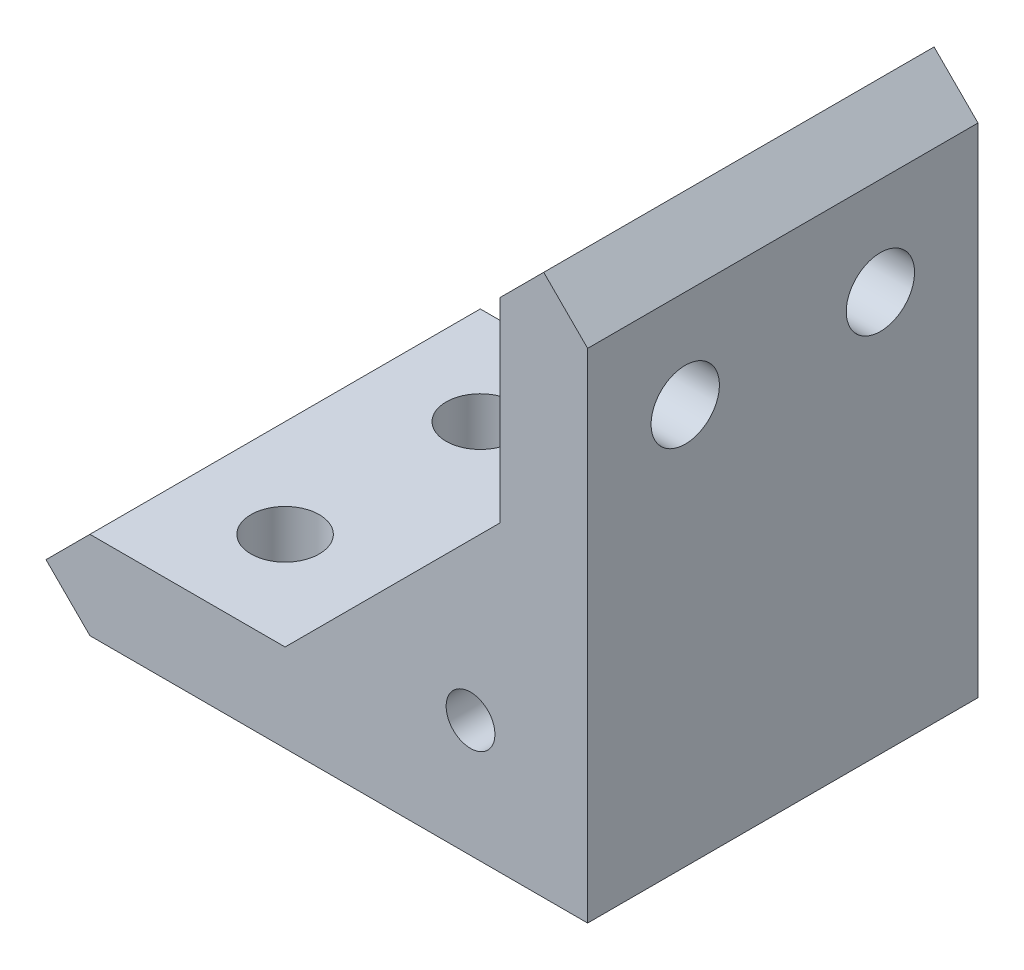
SolidWorks part; units mm, degrees
ref_plane "Front Plane" through (0, 0, 0) normal (0, 0, 1) x (1, 0, 0)
ref_plane "Top Plane" through (0, 0, 0) normal (0, 1, 0) x (1, 0, 0)
ref_plane "Right Plane" through (0, 0, 0) normal (1, 0, 0) x (0, 0, -1)
sketch "Sketch1" plane through (0, 0, 0) normal (0, 0, 1) x (1, 0, 0)
  line L0 (0, 56) -> (0, 0)
  line L1 (0, 0) -> (-56, 0)
  line L2 (-56, 0) -> (-56, 9)
  line L3 (-56, 9) -> (-31, 9)
  line L4 (-31, 9) -> (-9, 31)
  line L5 (-9, 31) -> (-9, 56)
  line L6 (-9, 56) -> (0, 56)
  dimension "D1" = 56
  dimension "D2" = 56
  dimension "D3" = 9
  dimension "D4" = 9
  dimension "D5" = 25
  dimension "D6" = 25
extrude "Boss-Extrude1" add sketch "Sketch1" along normal blind 40
sketch "Sketch2" plane through (-9, 0, 0) normal (-1, 0, 0) x (0, 0, 1)
  line L0 (0, 56) -> (0, 31) construction
  line L1 (40, 0) -> (0, 0) construction
  circle A0 centre (10, 41) radius 3.5
  circle A1 centre (30, 41) radius 3.5
  dimension "D1" = 7
  dimension "D2" = 7
  dimension "D3" = 10
  dimension "D4" = 20
  dimension "D5" = 41
extrude "Cut-Extrude1" cut sketch "Sketch2" against normal through all
sketch "Sketch3" plane through (0, 9, 0) normal (0, 1, 0) x (1, 0, 0)
  line L0 (-31, 0) -> (-56, 0) construction
  line L1 (0, -40) -> (0, 0) construction
  circle A0 centre (-41, -10) radius 3.5
  circle A1 centre (-41, -30) radius 3.5
  dimension "D1" = 7
  dimension "D2" = 7
  dimension "D3" = 10
  dimension "D4" = 20
  dimension "D5" = 41
extrude "Cut-Extrude2" cut sketch "Sketch3" against normal blind 40
chamfer "Chamfer1" distance 5 angle 45 4 edges at (-56, 0, 20) (-56, 9, 20) (0, 56, 20) (-9, 56, 20)
sketch "Sketch4" plane through (0, 0, 0) normal (0, 0, -1) x (-1, 0, 0)
  line L0 (51, 0) -> (0, 0) construction
  line L1 (0, 0) -> (0, 51) construction
  circle A0 centre (12, 12) radius 2.5
  dimension "D1" = 5
  dimension "D2" = 12
  dimension "D3" = 12
extrude "Cut-Extrude3" cut sketch "Sketch4" against normal blind 40
